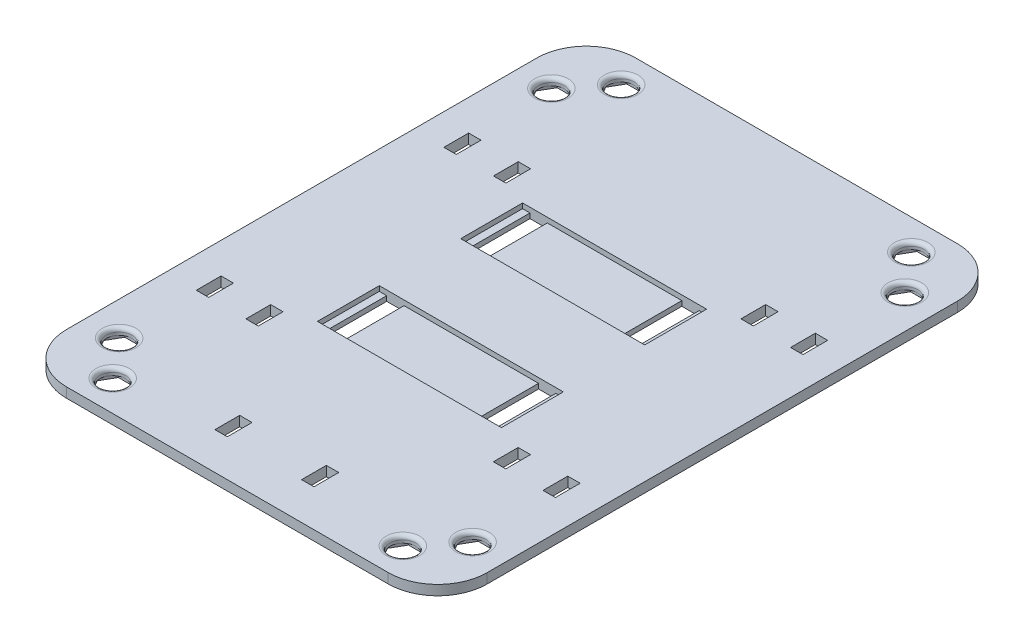
SolidWorks part; units mm, degrees
material "3-D Printed ABS"
ref_plane "Front Plane" through (0, 0, 0) normal (0, 0, 1) x (1, 0, 0)
ref_plane "Top Plane" through (0, 0, 0) normal (0, 1, 0) x (1, 0, 0)
ref_plane "Right Plane" through (0, 0, 0) normal (1, 0, 0) x (0, 0, -1)
sketch "Sketch1" plane through (0, 0, 0) normal (0, 1, 0) x (1, 0, 0)
  line L1 (-53.975, -73.025) -> (53.975, -73.025)
  line L2 (-53.975, -73.025) -> (-53.975, 73.025)
  line L3 (-53.975, 73.025) -> (53.975, 73.025)
  line L4 (53.975, -73.025) -> (53.975, 73.025)
  line L5 (-53.975, -73.025) -> (53.975, 73.025) construction
  line L6 (-53.975, 73.025) -> (53.975, -73.025) construction
  point P0 (0, 0)
  dimension "D1" = 107.95
  dimension "PlateY" = 146.05
extrude "Boss-Extrude1" add sketch "Sketch1" against normal blind 2.54
sketch "Sketch2" plane through (0, 0, 0) normal (0, 1, 0) x (1, 0, 0)
  line L0 (0, 0) -> (152.4, 0) construction
  line L1 (0, 0) -> (0, 152.4) construction
  line L4 (0, 0) -> (-53.975, 73.025) construction
  line L5 (0, 0) -> (-152.4, 0) construction
  line L6 (0, 0) -> (-152.4, 152.4) construction
  line L7 (-53.975, 73.025) -> (-53.975, -73.025) construction
  line L8 (53.975, 73.025) -> (-53.975, 73.025) construction
  line L9 (-152.4, 152.4) -> (-41.275, 60.325) construction
  line L10 (-41.275, 60.325) -> (0, 26.1257) construction
  line L11 (-30.7521, 73.025) -> (-53.975, 44.9974) construction
  circle A0 centre (-37.2189, 65.2108) radius 3.302
  circle A1 centre (45.3264, 55.4354) radius 3.302
  circle A2 centre (37.2189, 65.2108) radius 3.302
  circle A3 centre (-45.3264, -55.4354) radius 3.302
  circle A4 centre (-45.3264, 55.4354) radius 3.302
  circle A5 centre (-37.2189, -65.2108) radius 3.302
  circle A6 centre (37.2189, -65.2108) radius 3.302
  circle A7 centre (45.3264, -55.4354) radius 3.302
  point P12 (-41.275, 60.325)
  point P15 (-37.2189, 65.2108)
  dimension "D1" = 6.604
  dimension "D3" = 12.7
  dimension "D8" = 6.604
  dimension "D2" = 12.7
  dimension "D4" = 152.4
  dimension "D5" = 152.4
  dimension "D6" = 152.4
  dimension "D7" = 6.35
  dimension "D9" = 6.35
extrude "Cut-Extrude1" cut sketch "Sketch2" against normal through all
sketch "Sketch3" plane through (0, 0, 0) normal (0, 1, 0) x (1, 0, 0)
  line L0 (-53.975, 0) -> (53.975, 0) construction
  line L1 (-21.695, 26.3125) -> (-17.25, 26.3125)
  line L2 (-21.695, 26.3125) -> (-21.695, 10.4375)
  line L3 (-21.695, 10.4375) -> (-17.25, 10.4375)
  line L4 (-17.25, 26.3125) -> (-17.25, 10.4375)
  line L5 (17.25, 26.3125) -> (17.25, 10.4375)
  line L6 (21.695, 10.4375) -> (17.25, 10.4375)
  line L7 (21.695, 26.3125) -> (21.695, 10.4375)
  line L8 (21.695, 26.3125) -> (17.25, 26.3125)
  line L9 (-53.975, 73.025) -> (-53.975, -73.025) construction
  line L10 (53.975, -73.025) -> (53.975, 73.025) construction
  line L11 (0, -18.375) -> (0, 79.6704) construction
  line L12 (0, 18.375) -> (0, -79.6704) construction
  line L13 (21.695, -26.3125) -> (17.25, -26.3125)
  line L14 (21.695, -26.3125) -> (21.695, -10.4375)
  line L15 (21.695, -10.4375) -> (17.25, -10.4375)
  line L16 (17.25, -26.3125) -> (17.25, -10.4375)
  line L17 (-17.25, -26.3125) -> (-17.25, -10.4375)
  line L18 (-21.695, -10.4375) -> (-17.25, -10.4375)
  line L19 (-21.695, -26.3125) -> (-21.695, -10.4375)
  line L20 (-21.695, -26.3125) -> (-17.25, -26.3125)
  line L21 (-21.695, 18.375) -> (-33.6921, 18.375) construction
  line L22 (-53.975, -73.025) -> (53.975, -73.025) construction
  point P31 (0, -73.025)
  point P32 (-53.975, 0)
  dimension "D1" = 15.875
  dimension "D2" = 4.445
  dimension "D3" = 17.25
  dimension "D4" = 18.375
  dimension "D5" = 18.375
extrude "Cut-Extrude2" cut sketch "Sketch3" against normal through all
fillet "Fillet1" radius 12.7 4 edges at (53.975, -1.27, -73.025) (53.975, -1.27, 73.025) (-53.975, -1.27, 73.025) (-53.975, -1.27, -73.025)
sketch "Sketch4" plane through (0, 0, 0) normal (0, 1, 0) x (1, 0, 0)
  line L0 (0, 0) -> (80.9727, -80.9727) construction
  line L1 (0, 0) -> (-80.9727, -80.9727) construction
  line L2 (69.1118, -51.1513) -> (28.7006, -10.7401)
  line L3 (28.7006, -10.7401) -> (10.7401, -28.7006)
  line L4 (10.7401, -28.7006) -> (51.1513, -69.1118)
  line L5 (51.1513, -69.1118) -> (69.1118, -51.1513)
  line L6 (0, 0) -> (0, -118.7381) construction
  line L7 (0, 0) -> (-98.4177, 0) construction
  line L8 (-51.1513, -69.1118) -> (-69.1118, -51.1513)
  line L9 (-69.1118, -51.1513) -> (-28.7006, -10.7401)
  line L10 (-28.7006, -10.7401) -> (-10.7401, -28.7006)
  line L11 (-10.7401, -28.7006) -> (-51.1513, -69.1118)
  line L12 (-69.1118, 51.1513) -> (-28.7006, 10.7401)
  line L13 (-51.1513, 69.1118) -> (-69.1118, 51.1513)
  line L14 (-10.7401, 28.7006) -> (-51.1513, 69.1118)
  line L15 (-28.7006, 10.7401) -> (-10.7401, 28.7006)
  line L16 (51.1513, 69.1118) -> (69.1118, 51.1513)
  line L17 (69.1118, 51.1513) -> (28.7006, 10.7401)
  line L18 (28.7006, 10.7401) -> (10.7401, 28.7006)
  line L19 (10.7401, 28.7006) -> (51.1513, 69.1118)
  point P6 (19.7204, -19.7204)
  dimension "D1" = 25.4
  dimension "D2" = 57.15
  dimension "D3" = 45
extrude "Cut-Extrude3" [suppressed] cut sketch "Sketch4" against normal blind 1.5875
sketch "Sketch6" [suppressed] plane through (0, 0, 0) normal (0, 1, 0) x (1, 0, 0)
  line L0 (46.3377, -44.1074) -> (34.6634, -32.4331) construction
  line L1 (0, 0) -> (0, -117.7376) construction
  line L2 (0, 0) -> (-151.7285, 0) construction
  line L4 (28.1601, -10.1996) -> (10.1996, -28.1601) construction
  line L5 (50.6107, -68.5712) -> (68.5712, -50.6107) construction
  text T0 "ESC" font "Century Gothic" height in points 22
  dimension "D1" = 45
  dimension "D2" = 20.32
  dimension "D3" = 20.32
extrude "Cut-Extrude5" [suppressed] cut sketch "Sketch6" against normal blind 3.175
sketch "Sketch5" plane through (0, 0, 0) normal (0, 1, 0) x (1, 0, 0)
  line L0 (41.275, 73.025) -> (-41.275, 73.025) construction
  line L1 (14.2875, 15.875) -> (-14.2875, 15.875)
  line L2 (14.2875, 15.875) -> (14.2875, 66.675)
  line L3 (14.2875, 66.675) -> (-14.2875, 66.675)
  line L4 (-14.2875, 15.875) -> (-14.2875, 66.675)
  point P4 (0, 15.875)
  dimension "D1" = 50.8
  dimension "D2" = 28.575
  dimension "D3" = 6.35
extrude "Cut-Extrude4" [suppressed] cut sketch "Sketch5" against normal blind 1.5875
ref_axis "Axis1" through (0, 0.3175, 0) along (0, -1, 0)
pattern_circular "CirPattern1" [suppressed] count 4 over 360 about axis through (0, 0.3175, 0) along (0, -1, 0) of bodies 105
sketch "Sketch7" plane through (0, 0, 0) normal (0, 1, 0) x (1, 0, 0)
  line L0 (0, 0) -> (0, -54.962) construction
  line L1 (63.4018, -13.3522) -> (38.0018, -13.3522)
  line L2 (63.4018, -13.3522) -> (63.4018, 43.7978)
  line L3 (63.4018, 43.7978) -> (38.0018, 43.7978)
  line L4 (38.0018, -13.3522) -> (38.0018, 43.7978)
  line L5 (-38.0018, -13.3522) -> (-38.0018, 43.7978)
  line L6 (-63.4018, 43.7978) -> (-38.0018, 43.7978)
  line L7 (-63.4018, -13.3522) -> (-63.4018, 43.7978)
  line L8 (-63.4018, -13.3522) -> (-38.0018, -13.3522)
  line L9 (-41.275, -73.025) -> (41.275, -73.025) construction
  line L10 (38.5677, -40.64) -> (-18.5823, -40.64)
  line L11 (38.5677, -40.64) -> (38.5677, -66.04)
  line L12 (38.5677, -66.04) -> (-18.5823, -66.04)
  line L13 (-18.5823, -40.64) -> (-18.5823, -66.04)
  line L14 (38.5677, -40.64) -> (-18.5823, -66.04) construction
  line L15 (38.5677, -66.04) -> (-18.5823, -40.64) construction
  line L16 (19.844, -36.1003) -> (-37.306, -36.1003)
  line L17 (19.844, -36.1003) -> (19.844, -61.5003)
  line L18 (19.844, -61.5003) -> (-37.306, -61.5003)
  line L19 (-37.306, -36.1003) -> (-37.306, -61.5003)
  line L20 (19.844, -36.1003) -> (-37.306, -61.5003) construction
  line L21 (19.844, -61.5003) -> (-37.306, -36.1003) construction
  point P11 (9.9927, -53.34)
  point P18 (-8.731, -48.8003)
  dimension "D1" = 57.15
  dimension "D2" = 25.4
  dimension "D3" = 57.15
  dimension "D4" = 25.4
  dimension "D5" = 6.985
  dimension "D6" = 57.15
  dimension "D7" = 25.4
extrude "Cut-Extrude6" [suppressed] cut sketch "Sketch7" against normal blind 1.27
sketch "Sketch8" plane through (0, 0, 0) normal (0, 1, 0) x (1, 0, 0)
  line L7 (19.05, -31.75) -> (-19.05, -31.75)
  line L8 (19.05, -31.75) -> (19.05, 31.75)
  line L9 (19.05, 31.75) -> (-19.05, 31.75)
  line L10 (-19.05, -31.75) -> (-19.05, 31.75)
  point P0 (0, 0)
  dimension "D1" = 38.1
  dimension "D2" = 31.75
  dimension "D3" = 63.5
extrude "Boss-Extrude3" [suppressed] add sketch "Sketch8" along normal blind 2.54
sketch "Sketch11" plane through (0, 0, 0) normal (0, 1, 0) x (1, 0, 0)
  line L0 (-21.695, -26.3125) -> (-17.25, -26.3125) construction
  line L1 (23.6, -26.3125) -> (-23.6, -26.3125)
  line L2 (23.6, -26.3125) -> (23.6, -10.4375)
  line L3 (23.6, -10.4375) -> (-23.6, -10.4375)
  line L4 (-23.6, -26.3125) -> (-23.6, -10.4375)
  line L5 (21.695, -10.4375) -> (17.25, -10.4375) construction
  line L6 (21.695, -26.3125) -> (21.695, -10.4375) construction
  line L7 (-21.695, -10.4375) -> (-21.695, -26.3125) construction
  line L8 (0, 0) -> (90.9737, 0) construction
  line L9 (-23.6, 26.3125) -> (-23.6, 10.4375)
  line L10 (23.6, 10.4375) -> (-23.6, 10.4375)
  line L11 (23.6, 26.3125) -> (23.6, 10.4375)
  line L12 (23.6, 26.3125) -> (-23.6, 26.3125)
  dimension "D1" = 1.905
  dimension "D2" = 1.905
extrude "Cut-Extrude9" cut sketch "Sketch11" against normal mid plane 2.54
sketch "Sketch12" plane through (0, 0, 0) normal (0, 1, 0) x (1, 0, 0)
  line L1 (12.7, -34.5105) -> (-12.7, -34.5105)
  line L2 (12.7, -34.5105) -> (12.7, -18.375)
  line L3 (12.7, -18.375) -> (-12.7, -18.375)
  line L4 (-12.7, -34.5105) -> (-12.7, -18.375)
  line L6 (23.8125, 0) -> (-23.8125, 0) construction
  line L7 (-53.975, 60.325) -> (-53.975, -60.325) construction
  line L9 (-12.7, 34.5105) -> (-12.7, 18.375)
  line L10 (12.7, 18.375) -> (-12.7, 18.375)
  line L11 (12.7, 34.5105) -> (12.7, 18.375)
  line L12 (12.7, 34.5105) -> (-12.7, 34.5105)
  point P6 (-53.975, 0)
  dimension "D1" = 25.4
  dimension "D2" = 18.375
extrude "Cut-Extrude12" [suppressed] cut sketch "Sketch12" along normal through all
sketch "Sketch9" plane through (0, 0, 0) normal (0, 1, 0) x (1, 0, 0)
  line L1 (25.1579, -52.4084) -> (-25.6421, -52.4084)
  line L2 (25.1579, -52.4084) -> (25.1579, -1.6084)
  line L3 (25.1579, -1.6084) -> (-25.6421, -1.6084)
  line L4 (-25.6421, -52.4084) -> (-25.6421, -1.6084)
  line L5 (25.1579, -52.4084) -> (-25.6421, -1.6084) construction
  line L6 (25.1579, -1.6084) -> (-25.6421, -52.4084) construction
  point P0 (-0.2421, -27.0084)
  dimension "D1" = 50.8
  dimension "D2" = 50.8
sketch "Sketch13" plane through (0, 0, 0) normal (0, 1, 0) x (1, 0, 0)
  line L0 (0, 0) -> (0, -106.7514) construction
  line L1 (34.925, 3.175) -> (28.575, 3.175)
  line L2 (34.925, 3.175) -> (34.925, -3.175)
  line L3 (34.925, -3.175) -> (28.575, -3.175)
  line L4 (28.575, 3.175) -> (28.575, -3.175)
  line L5 (34.925, 3.175) -> (28.575, -3.175) construction
  line L6 (34.925, -3.175) -> (28.575, 3.175) construction
  line L7 (-34.925, -3.175) -> (-28.575, 3.175) construction
  line L8 (-34.925, 3.175) -> (-28.575, -3.175) construction
  line L9 (-28.575, 3.175) -> (-28.575, -3.175)
  line L10 (-34.925, -3.175) -> (-28.575, -3.175)
  line L11 (-34.925, 3.175) -> (-34.925, -3.175)
  line L12 (-34.925, 3.175) -> (-28.575, 3.175)
  point P0 (31.75, 0)
  point P12 (-31.75, 0)
  dimension "D1" = 6.35
  dimension "D2" = 28.575
  dimension "D3" = 0
extrude "Cut-Extrude13" [suppressed] cut sketch "Sketch13" against normal through all
fillet "Fillet2" radius 1.016 8 edges at (-37.2189, 0, -61.9088) (37.2189, 0, 68.5128) (45.3264, 0, 58.7374) (-37.2189, 0, 61.9088) (-45.3264, 0, 52.1334) (45.3264, 0, -58.7374) (37.2189, 0, -68.5128) (-45.3264, 0, -52.1334)
sketch "Sketch14" plane through (0, 0, 0) normal (0, 1, 0) x (1, 0, 0)
  line L0 (0, 76.698) -> (0, -76.698) construction
  line L1 (33.3248, -34.925) -> (30.1498, -34.925)
  line L2 (33.3248, -34.925) -> (33.3248, -28.575)
  line L3 (33.3248, -28.575) -> (30.1498, -28.575)
  line L4 (30.1498, -34.925) -> (30.1498, -28.575)
  line L5 (0, 0) -> (-92.4571, 0) construction
  line L6 (-30.1498, -34.925) -> (-30.1498, -28.575)
  line L7 (-33.3248, -28.575) -> (-30.1498, -28.575)
  line L8 (-33.3248, -34.925) -> (-33.3248, -28.575)
  line L9 (-33.3248, -34.925) -> (-30.1498, -34.925)
  line L10 (-33.3248, 34.925) -> (-30.1498, 34.925)
  line L11 (-33.3248, 34.925) -> (-33.3248, 28.575)
  line L12 (-33.3248, 28.575) -> (-30.1498, 28.575)
  line L13 (-30.1498, 34.925) -> (-30.1498, 28.575)
  line L14 (30.1498, 34.925) -> (30.1498, 28.575)
  line L15 (33.3248, 28.575) -> (30.1498, 28.575)
  line L16 (33.3248, 34.925) -> (33.3248, 28.575)
  line L17 (33.3248, 34.925) -> (30.1498, 34.925)
  line L18 (-41.275, -73.025) -> (41.275, -73.025) construction
  line L19 (-9.525, -63.5) -> (-9.525, -57.15)
  line L20 (12.7, -63.5) -> (9.525, -63.5)
  line L21 (12.7, -63.5) -> (12.7, -57.15)
  line L22 (12.7, -57.15) -> (9.525, -57.15)
  line L23 (38.1, -73.025) -> (38.1, 73.025) construction
  line L24 (41.275, 73.025) -> (-41.275, 73.025) construction
  line L25 (42.8752, 34.925) -> (46.0502, 34.925)
  line L26 (42.8752, 34.925) -> (42.8752, 28.575)
  line L27 (42.8752, 28.575) -> (46.0502, 28.575)
  line L28 (46.0502, 34.925) -> (46.0502, 28.575)
  line L29 (46.0502, -34.925) -> (46.0502, -28.575)
  line L30 (42.8752, -28.575) -> (46.0502, -28.575)
  line L31 (42.8752, -34.925) -> (42.8752, -28.575)
  line L32 (42.8752, -34.925) -> (46.0502, -34.925)
  line L33 (-46.0502, 34.925) -> (-46.0502, 28.575)
  line L34 (-42.8752, 28.575) -> (-46.0502, 28.575)
  line L35 (-42.8752, 34.925) -> (-42.8752, 28.575)
  line L36 (-42.8752, 34.925) -> (-46.0502, 34.925)
  line L37 (-42.8752, -34.925) -> (-46.0502, -34.925)
  line L38 (-42.8752, -34.925) -> (-42.8752, -28.575)
  line L39 (-42.8752, -28.575) -> (-46.0502, -28.575)
  line L40 (-46.0502, -34.925) -> (-46.0502, -28.575)
  line L41 (53.975, -50.8) -> (-53.975, -50.8) construction
  line L42 (53.975, -60.325) -> (53.975, 60.325) construction
  line L43 (-53.975, 60.325) -> (-53.975, -60.325) construction
  line L44 (0, -178.298) -> (0, -24.902) construction
  line L45 (9.525, -63.5) -> (9.525, -57.15)
  line L46 (-12.7, -57.15) -> (-9.525, -57.15)
  line L47 (-12.7, -63.5) -> (-12.7, -57.15)
  line L48 (-12.7, -63.5) -> (-9.525, -63.5)
  dimension "D2" = 3.175
  dimension "D3" = 6.35
  dimension "D4" = 28.575
  dimension "D5" = 3.175
  dimension "D6" = 6.35
  dimension "D7" = 9.525
  dimension "D8" = 9.525
  dimension "D9" = 38.1
  dimension "D10" = 22.225
  dimension "D11" = 30.1498
extrude "Cut-Extrude14" cut sketch "Sketch14" against normal through all
sketch "Sketch17" plane through (0, -2.54, 0) normal (0, -1, 0) x (1, 0, 0)
  line L0 (0, 0) -> (-152.4, 0) construction
  line L1 (0, 0) -> (0, -152.4) construction
  line L2 (0, -152.4) -> (-152.4, -152.4) construction
  line L3 (-152.4, -152.4) -> (-152.4, 0) construction
  line L4 (-152.4, -152.4) -> (0, 0) construction
  line L5 (41.275, -73.025) -> (-41.275, -73.025) construction
  line L6 (-53.975, -60.325) -> (-53.975, 60.325) construction
  line L7 (-152.4, -152.4) -> (-41.275, -60.325) construction
  line L8 (-41.275, -60.325) -> (0, -26.1257) construction
  line L9 (43.3467, -52.0064) -> (47.3061, -52.0064)
  line L10 (-41.3669, -55.4354) -> (-43.3467, -52.0064)
  line L11 (-43.3467, -52.0064) -> (-47.3061, -52.0064)
  line L12 (-47.3061, -52.0064) -> (-49.2859, -55.4354)
  line L13 (-49.2859, -55.4354) -> (-47.3061, -58.8644)
  line L14 (-47.3061, -58.8644) -> (-43.3467, -58.8644)
  line L15 (-43.3467, -58.8644) -> (-41.3669, -55.4354)
  line L16 (-33.2595, -65.2108) -> (-35.2392, -61.7818)
  line L17 (-35.2392, -61.7818) -> (-39.1987, -61.7818)
  line L18 (-39.1987, -61.7818) -> (-41.1784, -65.2108)
  line L19 (-41.1784, -65.2108) -> (-39.1987, -68.6398)
  line L20 (-39.1987, -68.6398) -> (-35.2392, -68.6398)
  line L21 (-35.2392, -68.6398) -> (-33.2595, -65.2108)
  line L22 (47.3061, -52.0064) -> (49.2859, -55.4354)
  line L23 (49.2859, -55.4354) -> (47.3061, -58.8644)
  line L24 (41.3669, -55.4354) -> (43.3467, -52.0064)
  line L25 (43.3467, -58.8644) -> (41.3669, -55.4354)
  line L26 (47.3061, -58.8644) -> (43.3467, -58.8644)
  line L27 (35.2392, -61.7818) -> (39.1987, -61.7818)
  line L28 (33.2595, -65.2108) -> (35.2392, -61.7818)
  line L29 (39.1987, -61.7818) -> (41.1784, -65.2108)
  line L30 (41.1784, -65.2108) -> (39.1987, -68.6398)
  line L31 (35.2392, -68.6398) -> (33.2595, -65.2108)
  line L32 (39.1987, -68.6398) -> (35.2392, -68.6398)
  line L33 (-41.3669, 55.4354) -> (-43.3467, 52.0064)
  line L34 (-43.3467, 52.0064) -> (-47.3061, 52.0064)
  line L35 (-47.3061, 52.0064) -> (-49.2859, 55.4354)
  line L36 (-49.2859, 55.4354) -> (-47.3061, 58.8644)
  line L37 (-47.3061, 58.8644) -> (-43.3467, 58.8644)
  line L38 (-43.3467, 58.8644) -> (-41.3669, 55.4354)
  line L39 (-33.2595, 65.2108) -> (-35.2392, 61.7818)
  line L40 (-35.2392, 61.7818) -> (-39.1987, 61.7818)
  line L41 (-39.1987, 61.7818) -> (-41.1784, 65.2108)
  line L42 (-41.1784, 65.2108) -> (-39.1987, 68.6398)
  line L43 (-39.1987, 68.6398) -> (-35.2392, 68.6398)
  line L44 (-35.2392, 68.6398) -> (-33.2595, 65.2108)
  line L45 (39.1987, 68.6398) -> (35.2392, 68.6398)
  line L46 (35.2392, 68.6398) -> (33.2595, 65.2108)
  line L47 (41.1784, 65.2108) -> (39.1987, 68.6398)
  line L48 (39.1987, 61.7818) -> (41.1784, 65.2108)
  line L49 (33.2595, 65.2108) -> (35.2392, 61.7818)
  line L50 (35.2392, 61.7818) -> (39.1987, 61.7818)
  line L51 (47.3061, 58.8644) -> (43.3467, 58.8644)
  line L52 (43.3467, 58.8644) -> (41.3669, 55.4354)
  line L53 (41.3669, 55.4354) -> (43.3467, 52.0064)
  line L54 (49.2859, 55.4354) -> (47.3061, 58.8644)
  line L55 (47.3061, 52.0064) -> (49.2859, 55.4354)
  line L56 (43.3467, 52.0064) -> (47.3061, 52.0064)
  circle A0 centre (-45.3264, -55.4354) radius 3.429 construction
  circle A1 centre (-37.2189, -65.2108) radius 3.429 construction
  point P0 (0, 0)
  point P6 (-41.275, -60.2488)
  dimension "D1" = 12.7762
  dimension "D2" = 12.7
  dimension "D3" = 6.858
  dimension "D4" = 6.858
extrude "Cut-Extrude15" cut sketch "Sketch17" against normal blind 0.7937
equation "\"Plate Dim Y\"= \"Plate Dim Y@Quad Assemb.SLDASM\""
equation "\"PlateY@Sketch1\" = \"Plate Dim Y\""
equation "\"D1@Sketch1\"= \"Plate Dim X\""
equation "\"D1@Boss-Extrude1\" = \"Plate Thickness\""
equation "\"Plate Dim X\"= \"Plate Dim X@Quad Assemb.SLDASM\""
equation "\"Plate Thickness\"= \"Plate Thickness@Quad Assemb.sldasm\""
equation "\"Batt X\"= \"Batt X@Quad Assemb.sldasm\""
equation "\"Batt Y\"= \"Batt Y@Quad Assemb.sldasm\""
equation "\"D3@Sketch3\"=\"Batt X\"/2"
equation "\"D4@Sketch3\"=\"Batt Y\"/4"
equation "\"D5@Sketch3\"=\"Batt Y\"*2/8"
equation "\"Dowell Width\"= \"Dowell Width@Quad Assemb.sldasm\""
equation "\"D1@Sketch2\"=\"Dowell Width\"+.01"
equation "\"D2@Sketch12\"=\"Batt Y\"/4"
equation "\"D7@Sketch2\"=\"Dowell Width\""
equation "\"D8@Sketch2\"=\"Dowell Width\" +0.01in"
equation "\"D9@Sketch2\"=\"Dowell Width\""
